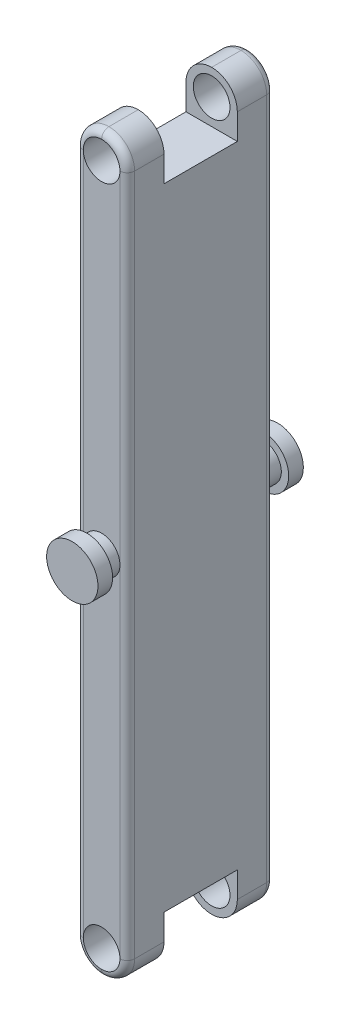
SolidWorks part; units mm, degrees
ref_plane "Front Plane" through (0, 0, 0) normal (0, 0, 1) x (1, 0, 0)
ref_plane "Top Plane" through (0, 0, 0) normal (0, 1, 0) x (1, 0, 0)
ref_plane "Right Plane" through (0, 0, 0) normal (1, 0, 0) x (0, 0, -1)
sketch "Sketch1" plane through (0, 0, 0) normal (0, 1, 0) x (1, 0, 0)
  line L1 (0, 0) -> (14, 0)
  line L2 (0, 0) -> (0, -20)
  line L3 (0, -20) -> (14, -20)
  line L4 (14, 0) -> (14, -20)
  dimension "D1" = 20
  dimension "D2" = 14
extrude "Boss-Extrude1" add sketch "Sketch1" along normal blind 200
sketch "Sketch2" plane through (0, 0, 0) normal (0, -1, 0) x (1, 0, 0)
  line L1 (14, 20) -> (14, 0) construction
  line L2 (0, 0) -> (14, 0)
  line L3 (0, 0) -> (0, 10)
  line L4 (0, 10) -> (14, 10)
  line L5 (14, 0) -> (14, 10)
  dimension "D1" = 10
extrude "Cut-Extrude1" cut sketch "Sketch2" against normal blind 14
sketch "Sketch4" plane through (0, 200, 0) normal (0, 1, 0) x (1, 0, 0)
  line L0 (14, -20) -> (14, 0) construction
  line L1 (0, 0) -> (14, 0)
  line L2 (0, 0) -> (0, -10)
  line L3 (0, -10) -> (14, -10)
  line L4 (14, 0) -> (14, -10)
  dimension "D1" = 10
sketch "Sketch5" plane through (0, 0, 10) normal (0, 0, -1) x (-1, 0, 0)
  circle A0 centre (-7, 7) radius 5
  dimension "D1" = 10
extrude "Cut-Extrude4" cut sketch "Sketch5" against normal blind 10
extrude "Cut-Extrude3" cut sketch "Sketch4" against normal blind 14
sketch "Sketch6" plane through (0, 0, 10) normal (0, 0, -1) x (-1, 0, 0)
  circle A0 centre (-7, 193) radius 5
  dimension "D1" = 10
extrude "Cut-Extrude5" cut sketch "Sketch6" against normal blind 10
mirror "Mirror1" about plane through (0, 200, 0) normal (0, 0, 1) of "Cut-Extrude5", "Cut-Extrude3", "Cut-Extrude4", "Cut-Extrude1", "Boss-Extrude1"
fillet "Fillet3" radius 7 8 edges at (0, 200, 15) (14, 200, 15) (0, 200, -15) (14, 200, -15) (0, 0, -15) (14, 0, -15) (0, 0, 15) (14, 0, 15)
sketch "Sketch7" plane through (0, 0, 20) normal (0, 0, 1) x (1, 0, 0)
  circle A0 centre (7, 100) radius 5
  dimension "D1" = 10
extrude "Boss-Extrude2" add sketch "Sketch7" along normal blind 4
sketch "Sketch8" plane through (0, 0, 24) normal (0, 0, 1) x (1, 0, 0)
  circle A0 centre (7, 100) radius 7
  dimension "D1" = 14
extrude "Boss-Extrude3" add sketch "Sketch8" along normal blind 4
mirror "Mirror2" about plane through (0, 0, 0) normal (0, 0, 1) of "Boss-Extrude3", "Boss-Extrude2"
fillet "Fillet2" radius 2 12 edges at (0, 100, -20) (0, 100, 20) (14, 100, -20) (14, 100, 20) (11.9497, 197.9497, -20) (2.0503, 197.9497, -20) (2.0503, 2.0503, -20) (11.9497, 2.0503, -20) (11.9497, 197.9497, 20) (2.0503, 197.9497, 20) (2.0503, 2.0503, 20) (11.9497, 2.0503, 20)
